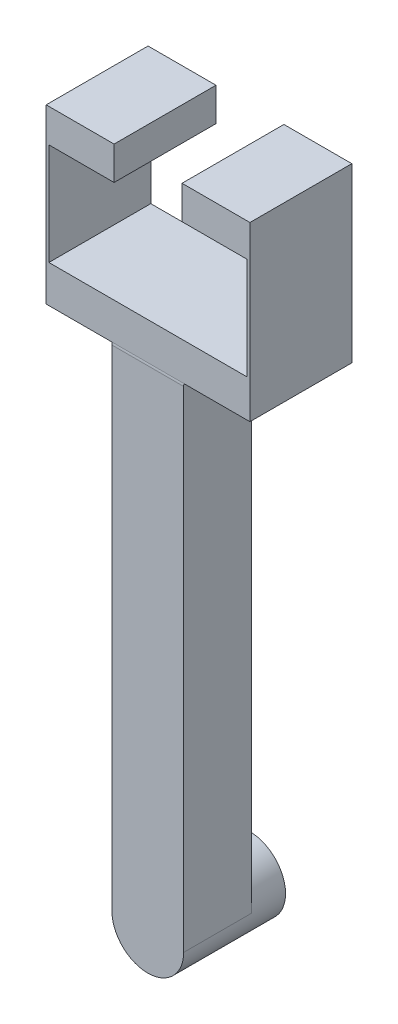
SolidWorks part; units mm, degrees
material "6061-T6 (SS)"
ref_plane "Front Plane" through (0, 0, 0) normal (0, 0, 1) x (1, 0, 0)
ref_plane "Top Plane" through (0, 0, 0) normal (0, 1, 0) x (1, 0, 0)
ref_plane "Right Plane" through (0, 0, 0) normal (1, 0, 0) x (0, 0, -1)
sketch "Sketch2" plane through (0, 0, 0) normal (0, 0, 1) x (1, 0, 0)
  circle A0 centre (0, 0) radius 13.4112
  dimension "D1" = 26.8224
extrude "Boss-Extrude1" add sketch "Sketch2" along normal blind 38.1
sketch "Sketch5" plane through (0, 0, 38.1) normal (0, 0, 1) x (1, 0, 0)
  line L1 (-13.4112, 0) -> (13.4112, 0)
  line L2 (-13.4112, 0) -> (-13.4112, 184.15)
  line L3 (-13.4112, 184.15) -> (13.4112, 184.15)
  line L4 (13.4112, 0) -> (13.4112, 184.15)
  circle A0 centre (0, 0) radius 13.4112 construction
  dimension "D1" = 26.8224
  dimension "D2" = 184.15
extrude "Boss-Extrude2" add sketch "Sketch5" against normal blind 25.4
sketch "Sketch8" plane through (0, 184.15, 0) normal (0, 1, 0) x (1, 0, 0)
  line L1 (-38.1, 0.1018) -> (38.1, 0.1018)
  line L3 (-38.1, 0.1018) -> (-38.1, -37.9982)
  line L4 (-38.1, -37.9982) -> (38.1, -37.9982)
  line L5 (38.1, 0.1018) -> (38.1, -37.9982)
  dimension "D1" = 38.1
  dimension "D2" = 76.2
extrude "Boss-Extrude3" add sketch "Sketch8" along normal blind 13.97
sketch "Sketch9" plane through (0, 198.12, 0) normal (0, 1, 0) x (1, 0, 0)
  line L0 (-38.1, -37.9982) -> (38.1, -37.9982) construction
  line L1 (-38.1, 0.1018) -> (-37.084, 0.1018)
  line L2 (-38.1, 0.1018) -> (-38.1, -37.9982)
  line L3 (-38.1, -37.9982) -> (-37.084, -37.9982)
  line L4 (-37.084, 0.1018) -> (-37.084, -37.9982)
  line L6 (38.1, 0.1018) -> (37.084, 0.1018)
  line L7 (38.1, 0.1018) -> (38.1, -37.9982)
  line L8 (38.1, -37.9982) -> (37.084, -37.9982)
  line L9 (37.084, 0.1018) -> (37.084, -37.9982)
  dimension "D1" = 1.016
  dimension "D2" = 1.016
extrude "Boss-Extrude4" add sketch "Sketch9" along normal blind 38.1
sketch "Sketch10" plane through (0, 236.22, 0) normal (0, 1, 0) x (1, 0, 0)
  line L0 (-37.084, -37.9982) -> (37.084, -37.9982) construction
  line L1 (-38.1, 0.1018) -> (-12.7, 0.1018)
  line L2 (-38.1, 0.1018) -> (-38.1, -37.9982)
  line L3 (-38.1, -37.9982) -> (-12.7, -37.9982)
  line L4 (-12.7, 0.1018) -> (-12.7, -37.9982)
  line L6 (38.1, 0.1018) -> (12.7, 0.1018)
  line L7 (38.1, 0.1018) -> (38.1, -37.9982)
  line L8 (38.1, -37.9982) -> (12.7, -37.9982)
  line L9 (12.7, 0.1018) -> (12.7, -37.9982)
  dimension "D1" = 25.4
  dimension "D2" = 25.4
extrude "Boss-Extrude5" add sketch "Sketch10" along normal blind 12.446
fillet "Fillet1" radius 3.81 1 edges at (0, 184.15, 38.1)
equation "\"F\"= 600"
equation "\"Sy\"= 40000"
equation "\"E\"= 10000000"
equation "\"Defmax\"= 0.005in"
equation "\"a\"= 0.498in"
equation "\"b\"= 0.9992in"
equation "\"c\"= 1.499in"
equation "\"d\"= 2.4964in"
equation "\"rA\"= 0.528in"
equation "\"aB\"= 0.696in"
equation "\"tB\"= ( ( 1200 * 7.25 * 4 ) / ( \"E\" * \"Defmax\" ) ) / 1.15"
equation "\"hC\"= 0.5473in"
equation "\"LC\"= 2.4964in"
equation "\"WC\"= 1.5in"
equation "\"aD\"= 0.06in"
equation "\"DL\"= ( ( 600 / 1000 ) / \"WD\" )"
equation "\"WD\"= 1.499in"
equation "\"eH\"= 0.4897in"
equation "\"LE\"= 0.9992in"
equation "\"WE\"= 1.50in"
equation "\"D1@Sketch2\"= \"rA\" * 2"
equation "\"LA\"= 1.5in"
